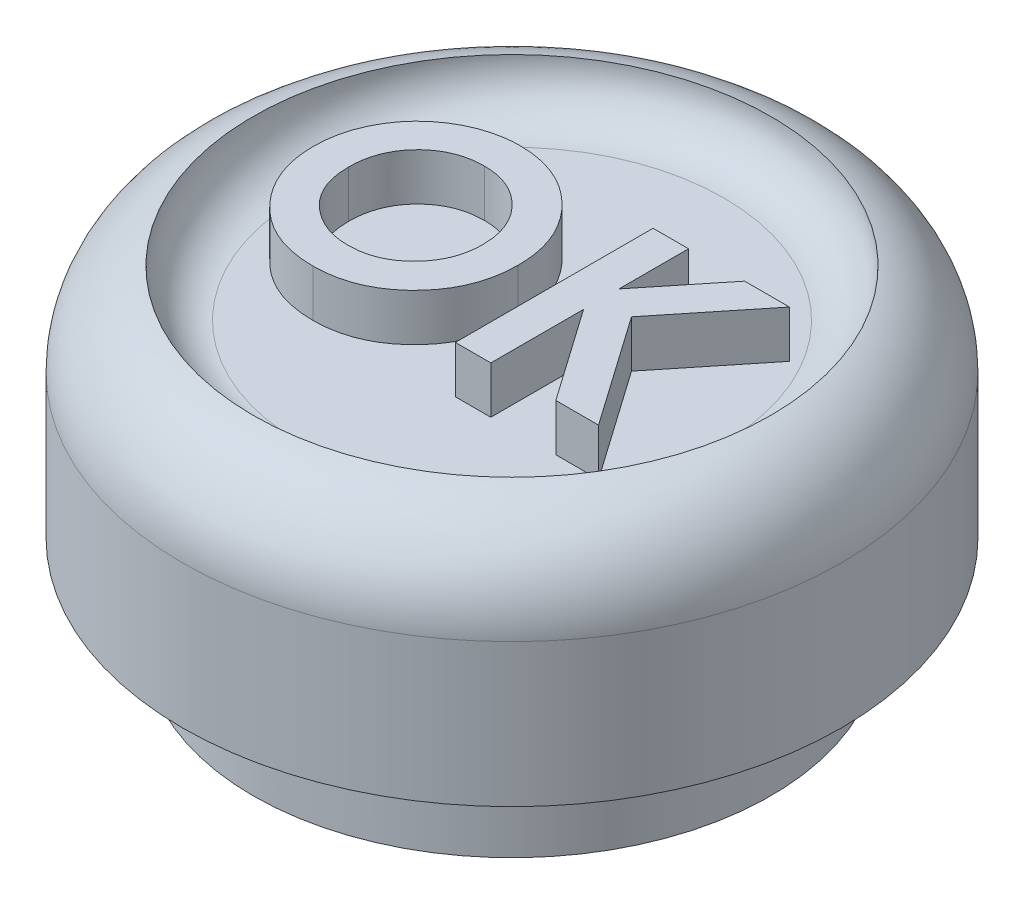
SolidWorks part; units mm, degrees
ref_plane "Спереди" through (0, 0, 0) normal (0, 0, 1) x (1, 0, 0)
ref_plane "Сверху" through (0, 0, 0) normal (0, 1, 0) x (1, 0, 0)
ref_plane "Справа" through (0, 0, 0) normal (1, 0, 0) x (0, 0, -1)
sketch "Эскиз1" plane through (0, 0, 0) normal (0, 1, 0) x (1, 0, 0)
  circle A0 centre (0, 0) radius 5.5
extrude "Бобышка-Вытянуть1" add sketch "Эскиз1" along normal blind 7
sketch "Эскиз6" plane through (0, 0, 0) normal (0, 0, 1) x (1, 0, 0)
  line L0 (-1000, 0) -> (49000, 0) construction
  line L1 (-5.5, 0) -> (5.5, 0) construction
  line L2 (0, -1000) -> (0, 49000) construction
  line L3 (-7, -1000) -> (-7, 49000) construction
  line L4 (-999.6295, 7) -> (49000.3705, 7) construction
  line L6 (-999.6295, 3) -> (49000.3705, 3) construction
  line L11 (-5.5, -993) -> (-5.5, 49007) construction
  line L12 (-4.6652, 2) -> (-7, 2)
  line L13 (-5.5, 7) -> (-4.6652, 7)
  line L14 (-4.6652, 7) -> (-4.6652, 3)
  line L16 (-7, 3) -> (-7, 5.0359)
  line L17 (-4.6652, 3) -> (-4.6652, 2)
  line L18 (-7, 2) -> (-7, 3)
  circle A2 centre (-4.9641, 5.0359) radius 2.0359 construction
  arc A3 (-7, 5.0359) -> (-5.5, 7) centre (-4.9641, 5.0359) cw
  point P5 (0, 0)
  point P15 (-5.5, 7)
revolve "Повернуть3" add sketch "Эскиз6" angle 360 about L2
sketch "Эскиз2" plane through (0, 7, 0) normal (0, 1, 0) x (1, 0, 0)
  circle A0 centre (0, 0) radius 5.5
extrude "Вырез-Вытянуть1" cut sketch "Эскиз2" against normal blind 1
sketch "Эскиз3" plane through (0, 6, 0) normal (0, 1, 0) x (1, 0, 0)
  line L0 (-1000, 0) -> (49000, 0) construction
  line L1 (0, -1000) -> (0, 49000) construction
  line L4 (-1000, -4) -> (49000, -4) construction
  line L5 (-1000, 4) -> (49000, 4) construction
  line L6 (-4, -1000) -> (-4, 49000) construction
  line L7 (4, -1000) -> (4, 49000) construction
  circle A0 centre (0, 0) radius 5 construction
  text T0 "<b>OK</b>" font "Century Gothic" height 4.2
extrude "Бобышка-Вытянуть2" add sketch "Эскиз3" along normal blind 1
sketch "Эскиз5" plane through (0, 0, 0) normal (0, -1, 0) x (1, 0, 0)
  line L0 (0, -1000) -> (0, 49000) construction
  line L1 (-1000, 0) -> (49000, 0) construction
  line L2 (-2, -2) -> (2, -2)
  line L3 (2, -2) -> (2, 2)
  line L4 (-2, 2) -> (2, 2)
  line L5 (-2, -2) -> (-2, 2)
  line L7 (-2, -1000) -> (-2, 49000) construction
  line L8 (2, -1000) -> (2, 49000) construction
  line L9 (-1000, 2) -> (49000, 2) construction
  line L10 (-1000, -2) -> (49000, -2) construction
  dimension "D1" = 2
  dimension "D2" = 2
extrude "Вырез-Вытянуть2" cut sketch "Эскиз5" against normal blind 3
fillet "Скругление3" radius 1 1 edges at (0, 6, 5.5)
